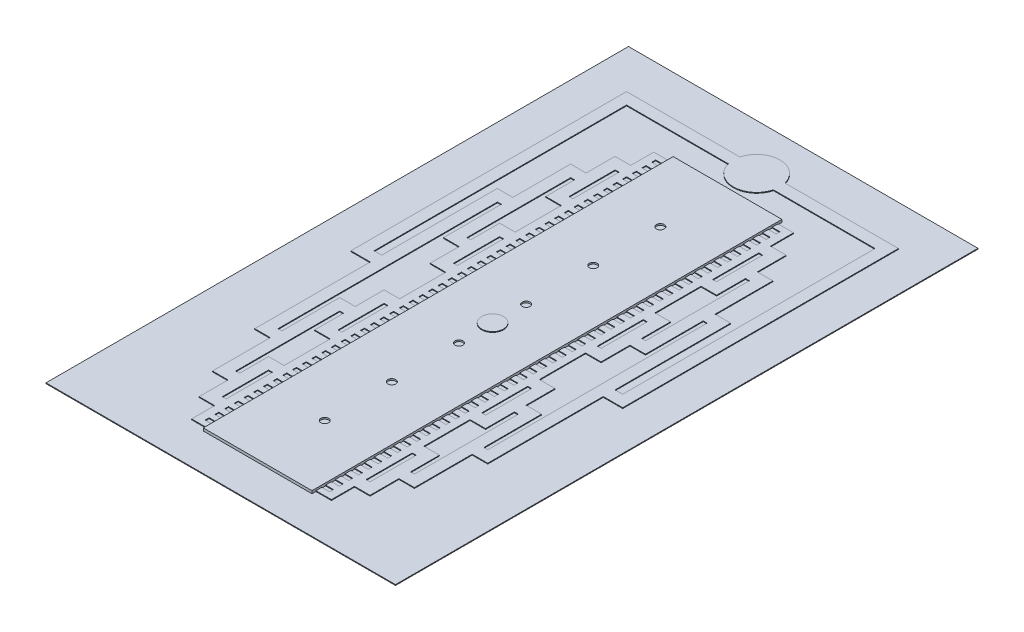
SolidWorks part; units mm, degrees
ref_plane "Front Plane" through (0, 0, 0) normal (0, 0, 1) x (1, 0, 0)
ref_plane "Top Plane" through (0, 0, 0) normal (0, 1, 0) x (1, 0, 0)
ref_plane "Right Plane" through (0, 0, 0) normal (1, 0, 0) x (0, 0, -1)
sketch "Sketch2" plane through (0, 0, 0) normal (0, 1, 0) x (1, 0, 0)
  line L1 (-22.5, 37.5) -> (22.5, 37.5)
  line L2 (-22.5, 37.5) -> (-22.5, -37.5)
  line L3 (-22.5, -37.5) -> (22.5, -37.5)
  line L4 (22.5, 37.5) -> (22.5, -37.5)
  line L5 (-22.5, 37.5) -> (22.5, -37.5) construction
  line L6 (-22.5, -37.5) -> (22.5, 37.5) construction
  point P0 (0, 0)
extrude "Boss-Extrude1" add sketch "Sketch2" along normal blind 0.1
sketch "Sketch3" plane through (0, 0.1, 0) normal (0, 1, 0) x (1, 0, 0)
  line L1 (-7, 30.25) -> (7, 30.25)
  line L2 (-7, 30.25) -> (-7, -30.25)
  line L3 (-7, -30.25) -> (7, -30.25)
  line L4 (7, 30.25) -> (7, -30.25)
  line L5 (-7, 30.25) -> (7, -30.25) construction
  line L6 (-7, -30.25) -> (7, 30.25) construction
  point P0 (0, 0)
extrude "Boss-Extrude2" add sketch "Sketch3" along normal blind 0.35
sketch "Sketch4" plane through (0, 0.1, 0) normal (0, 1, 0) x (1, 0, 0)
  line L0 (7, 29.75) -> (9, 29.75)
  line L1 (7, 29.75) -> (7, -29.75)
  line L2 (9, 29.75) -> (9, -29.75)
  line L3 (7, -29.75) -> (9, -29.75)
  line L4 (7, -30.25) -> (7, 30.25) construction
  line L5 (0, 31.7119) -> (0, -31.7119) construction
  line L6 (-9, 29.75) -> (-9, -29.75)
  line L7 (-7, -29.75) -> (-9, -29.75)
  line L8 (-7, 29.75) -> (-7, -29.75)
  line L9 (-7, 29.75) -> (-9, 29.75)
  point P6 (9, 0)
  point P11 (0, 0)
extrude "Boss-Extrude3" add sketch "Sketch4" along normal blind 0.1
sketch "Sketch5" plane through (0, 0.2, 0) normal (0, 1, 0) x (1, 0, 0)
  line L0 (7, 29) -> (8, 29)
  line L1 (7, 29) -> (7, 28.5)
  line L2 (8, 29) -> (8, 28.5)
  line L3 (7, 28.5) -> (8, 28.5)
  line L4 (7, -30.25) -> (7, 30.25) construction
  line L5 (-8, 29) -> (-7, 29)
  line L6 (-8, 29) -> (-8, 28.5)
  line L7 (-8, 28.5) -> (-7, 28.5)
  line L8 (-7, 29) -> (-7, 28.5)
  line L9 (-8, 27.75) -> (-7, 27.75)
  line L10 (-8, 27.75) -> (-8, 27.25)
  line L11 (-8, 27.25) -> (-7, 27.25)
  line L12 (-7, 27.75) -> (-7, 27.25)
  line L13 (-8, 26.5) -> (-7, 26.5)
  line L14 (-8, 26.5) -> (-8, 26)
  line L15 (-8, 26) -> (-7, 26)
  line L16 (-7, 26.5) -> (-7, 26)
  line L17 (-8, 25.25) -> (-7, 25.25)
  line L18 (-8, 25.25) -> (-8, 24.75)
  line L19 (-8, 24.75) -> (-7, 24.75)
  line L20 (-7, 25.25) -> (-7, 24.75)
  line L21 (-8, 24) -> (-7, 24)
  line L22 (-8, 24) -> (-8, 23.5)
  line L23 (-8, 23.5) -> (-7, 23.5)
  line L24 (-7, 24) -> (-7, 23.5)
  line L25 (-8, 22.75) -> (-7, 22.75)
  line L26 (-8, 22.75) -> (-8, 22.25)
  line L27 (-8, 22.25) -> (-7, 22.25)
  line L28 (-7, 22.75) -> (-7, 22.25)
  line L29 (-8, 21.5) -> (-7, 21.5)
  line L30 (-8, 21.5) -> (-8, 21)
  line L31 (-8, 21) -> (-7, 21)
  line L32 (-7, 21.5) -> (-7, 21)
  line L33 (-8, 20.25) -> (-7, 20.25)
  line L34 (-8, 20.25) -> (-8, 19.75)
  line L35 (-8, 19.75) -> (-7, 19.75)
  line L36 (-7, 20.25) -> (-7, 19.75)
  line L37 (-8, 19) -> (-7, 19)
  line L38 (-8, 19) -> (-8, 18.5)
  line L39 (-8, 18.5) -> (-7, 18.5)
  line L40 (-7, 19) -> (-7, 18.5)
  line L41 (-8, 17.75) -> (-7, 17.75)
  line L42 (-8, 17.75) -> (-8, 17.25)
  line L43 (-8, 17.25) -> (-7, 17.25)
  line L44 (-7, 17.75) -> (-7, 17.25)
  line L45 (-8, 16.5) -> (-7, 16.5)
  line L46 (-8, 16.5) -> (-8, 16)
  line L47 (-8, 16) -> (-7, 16)
  line L48 (-7, 16.5) -> (-7, 16)
  line L49 (-8, 15.25) -> (-7, 15.25)
  line L50 (-8, 15.25) -> (-8, 14.75)
  line L51 (-8, 14.75) -> (-7, 14.75)
  line L52 (-7, 15.25) -> (-7, 14.75)
  line L53 (-8, 14) -> (-7, 14)
  line L54 (-8, 14) -> (-8, 13.5)
  line L55 (-8, 13.5) -> (-7, 13.5)
  line L56 (-7, 14) -> (-7, 13.5)
  line L57 (-8, 12.75) -> (-7, 12.75)
  line L58 (-8, 12.75) -> (-8, 12.25)
  line L59 (-8, 12.25) -> (-7, 12.25)
  line L60 (-7, 12.75) -> (-7, 12.25)
  line L61 (-8, 11.5) -> (-7, 11.5)
  line L62 (-8, 11.5) -> (-8, 11)
  line L63 (-8, 11) -> (-7, 11)
  line L64 (-7, 11.5) -> (-7, 11)
  line L65 (-8, 10.25) -> (-7, 10.25)
  line L66 (-8, 10.25) -> (-8, 9.75)
  line L67 (-8, 9.75) -> (-7, 9.75)
  line L68 (-7, 10.25) -> (-7, 9.75)
  line L69 (-8, 9) -> (-7, 9)
  line L70 (-8, 9) -> (-8, 8.5)
  line L71 (-8, 8.5) -> (-7, 8.5)
  line L72 (-7, 9) -> (-7, 8.5)
  line L73 (-8, 7.75) -> (-7, 7.75)
  line L74 (-8, 7.75) -> (-8, 7.25)
  line L75 (-8, 7.25) -> (-7, 7.25)
  line L76 (-7, 7.75) -> (-7, 7.25)
  line L77 (-8, 6.5) -> (-7, 6.5)
  line L78 (-8, 6.5) -> (-8, 6)
  line L79 (-8, 6) -> (-7, 6)
  line L80 (-7, 6.5) -> (-7, 6)
  line L81 (-8, 5.25) -> (-7, 5.25)
  line L82 (-8, 5.25) -> (-8, 4.75)
  line L83 (-8, 4.75) -> (-7, 4.75)
  line L84 (-7, 5.25) -> (-7, 4.75)
  line L85 (-8, 4) -> (-7, 4)
  line L86 (-8, 4) -> (-8, 3.5)
  line L87 (-8, 3.5) -> (-7, 3.5)
  line L88 (-7, 4) -> (-7, 3.5)
  line L89 (-8, 2.75) -> (-7, 2.75)
  line L90 (-8, 2.75) -> (-8, 2.25)
  line L91 (-8, 2.25) -> (-7, 2.25)
  line L92 (-7, 2.75) -> (-7, 2.25)
  line L93 (-8, 1.5) -> (-7, 1.5)
  line L94 (-8, 1.5) -> (-8, 1)
  line L95 (-8, 1) -> (-7, 1)
  line L96 (-7, 1.5) -> (-7, 1)
  line L97 (-8, 0.25) -> (-7, 0.25)
  line L98 (-8, 0.25) -> (-8, -0.25)
  line L99 (-8, -0.25) -> (-7, -0.25)
  line L100 (-7, 0.25) -> (-7, -0.25)
  line L101 (-8, -1) -> (-7, -1)
  line L102 (-8, -1) -> (-8, -1.5)
  line L103 (-8, -1.5) -> (-7, -1.5)
  line L104 (-7, -1) -> (-7, -1.5)
  line L105 (-8, -2.25) -> (-7, -2.25)
  line L106 (-8, -2.25) -> (-8, -2.75)
  line L107 (-8, -2.75) -> (-7, -2.75)
  line L108 (-7, -2.25) -> (-7, -2.75)
  line L109 (-8, -3.5) -> (-7, -3.5)
  line L110 (-8, -3.5) -> (-8, -4)
  line L111 (-8, -4) -> (-7, -4)
  line L112 (-7, -3.5) -> (-7, -4)
  line L113 (-8, -4.75) -> (-7, -4.75)
  line L114 (-8, -4.75) -> (-8, -5.25)
  line L115 (-8, -5.25) -> (-7, -5.25)
  line L116 (-7, -4.75) -> (-7, -5.25)
  line L117 (-8, -6) -> (-7, -6)
  line L118 (-8, -6) -> (-8, -6.5)
  line L119 (-8, -6.5) -> (-7, -6.5)
  line L120 (-7, -6) -> (-7, -6.5)
  line L121 (-8, -7.25) -> (-7, -7.25)
  line L122 (-8, -7.25) -> (-8, -7.75)
  line L123 (-8, -7.75) -> (-7, -7.75)
  line L124 (-7, -7.25) -> (-7, -7.75)
  line L125 (-8, -8.5) -> (-7, -8.5)
  line L126 (-8, -8.5) -> (-8, -9)
  line L127 (-8, -9) -> (-7, -9)
  line L128 (-7, -8.5) -> (-7, -9)
  line L129 (-8, -9.75) -> (-7, -9.75)
  line L130 (-8, -9.75) -> (-8, -10.25)
  line L131 (-8, -10.25) -> (-7, -10.25)
  line L132 (-7, -9.75) -> (-7, -10.25)
  line L133 (-8, -11) -> (-7, -11)
  line L134 (-8, -11) -> (-8, -11.5)
  line L135 (-8, -11.5) -> (-7, -11.5)
  line L136 (-7, -11) -> (-7, -11.5)
  line L137 (-8, -12.25) -> (-7, -12.25)
  line L138 (-8, -12.25) -> (-8, -12.75)
  line L139 (-8, -12.75) -> (-7, -12.75)
  line L140 (-7, -12.25) -> (-7, -12.75)
  line L141 (-8, -13.5) -> (-7, -13.5)
  line L142 (-8, -13.5) -> (-8, -14)
  line L143 (-8, -14) -> (-7, -14)
  line L144 (-7, -13.5) -> (-7, -14)
  line L145 (-8, -14.75) -> (-7, -14.75)
  line L146 (-8, -14.75) -> (-8, -15.25)
  line L147 (-8, -15.25) -> (-7, -15.25)
  line L148 (-7, -14.75) -> (-7, -15.25)
  line L149 (-8, -16) -> (-7, -16)
  line L150 (-8, -16) -> (-8, -16.5)
  line L151 (-8, -16.5) -> (-7, -16.5)
  line L152 (-7, -16) -> (-7, -16.5)
  line L153 (-8, -17.25) -> (-7, -17.25)
  line L154 (-8, -17.25) -> (-8, -17.75)
  line L155 (-8, -17.75) -> (-7, -17.75)
  line L156 (-7, -17.25) -> (-7, -17.75)
  line L157 (-8, -18.5) -> (-7, -18.5)
  line L158 (-8, -18.5) -> (-8, -19)
  line L159 (-8, -19) -> (-7, -19)
  line L160 (-7, -18.5) -> (-7, -19)
  line L161 (-8, -19.75) -> (-7, -19.75)
  line L162 (-8, -19.75) -> (-8, -20.25)
  line L163 (-8, -20.25) -> (-7, -20.25)
  line L164 (-7, -19.75) -> (-7, -20.25)
  line L165 (-8, -21) -> (-7, -21)
  line L166 (-8, -21) -> (-8, -21.5)
  line L167 (-8, -21.5) -> (-7, -21.5)
  line L168 (-7, -21) -> (-7, -21.5)
  line L169 (-8, -22.25) -> (-7, -22.25)
  line L170 (-8, -22.25) -> (-8, -22.75)
  line L171 (-8, -22.75) -> (-7, -22.75)
  line L172 (-7, -22.25) -> (-7, -22.75)
  line L173 (-8, -23.5) -> (-7, -23.5)
  line L174 (-8, -23.5) -> (-8, -24)
  line L175 (-8, -24) -> (-7, -24)
  line L176 (-7, -23.5) -> (-7, -24)
  line L177 (-8, -24.75) -> (-7, -24.75)
  line L178 (-8, -24.75) -> (-8, -25.25)
  line L179 (-8, -25.25) -> (-7, -25.25)
  line L180 (-7, -24.75) -> (-7, -25.25)
  line L181 (-8, -26) -> (-7, -26)
  line L182 (-8, -26) -> (-8, -26.5)
  line L183 (-8, -26.5) -> (-7, -26.5)
  line L184 (-7, -26) -> (-7, -26.5)
  line L185 (-8, -27.25) -> (-7, -27.25)
  line L186 (-8, -27.25) -> (-8, -27.75)
  line L187 (-8, -27.75) -> (-7, -27.75)
  line L188 (-7, -27.25) -> (-7, -27.75)
  line L189 (-8, -28.5) -> (-7, -28.5)
  line L190 (-8, -28.5) -> (-8, -29)
  line L191 (-8, -29) -> (-7, -29)
  line L192 (-7, -28.5) -> (-7, -29)
  line L193 (7, 27.75) -> (8, 27.75)
  line L194 (7, 27.75) -> (7, 27.25)
  line L195 (7, 27.25) -> (8, 27.25)
  line L196 (8, 27.75) -> (8, 27.25)
  line L197 (7, 26.5) -> (8, 26.5)
  line L198 (7, 26.5) -> (7, 26)
  line L199 (7, 26) -> (8, 26)
  line L200 (8, 26.5) -> (8, 26)
  line L201 (7, 25.25) -> (8, 25.25)
  line L202 (7, 25.25) -> (7, 24.75)
  line L203 (7, 24.75) -> (8, 24.75)
  line L204 (8, 25.25) -> (8, 24.75)
  line L205 (7, 24) -> (8, 24)
  line L206 (7, 24) -> (7, 23.5)
  line L207 (7, 23.5) -> (8, 23.5)
  line L208 (8, 24) -> (8, 23.5)
  line L209 (7, 22.75) -> (8, 22.75)
  line L210 (7, 22.75) -> (7, 22.25)
  line L211 (7, 22.25) -> (8, 22.25)
  line L212 (8, 22.75) -> (8, 22.25)
  line L213 (7, 21.5) -> (8, 21.5)
  line L214 (7, 21.5) -> (7, 21)
  line L215 (7, 21) -> (8, 21)
  line L216 (8, 21.5) -> (8, 21)
  line L217 (7, 20.25) -> (8, 20.25)
  line L218 (7, 20.25) -> (7, 19.75)
  line L219 (7, 19.75) -> (8, 19.75)
  line L220 (8, 20.25) -> (8, 19.75)
  line L221 (7, 19) -> (8, 19)
  line L222 (7, 19) -> (7, 18.5)
  line L223 (7, 18.5) -> (8, 18.5)
  line L224 (8, 19) -> (8, 18.5)
  line L225 (7, 17.75) -> (8, 17.75)
  line L226 (7, 17.75) -> (7, 17.25)
  line L227 (7, 17.25) -> (8, 17.25)
  line L228 (8, 17.75) -> (8, 17.25)
  line L229 (7, 16.5) -> (8, 16.5)
  line L230 (7, 16.5) -> (7, 16)
  line L231 (7, 16) -> (8, 16)
  line L232 (8, 16.5) -> (8, 16)
  line L233 (7, 15.25) -> (8, 15.25)
  line L234 (7, 15.25) -> (7, 14.75)
  line L235 (7, 14.75) -> (8, 14.75)
  line L236 (8, 15.25) -> (8, 14.75)
  line L237 (7, 14) -> (8, 14)
  line L238 (7, 14) -> (7, 13.5)
  line L239 (7, 13.5) -> (8, 13.5)
  line L240 (8, 14) -> (8, 13.5)
  line L241 (7, 12.75) -> (8, 12.75)
  line L242 (7, 12.75) -> (7, 12.25)
  line L243 (7, 12.25) -> (8, 12.25)
  line L244 (8, 12.75) -> (8, 12.25)
  line L245 (7, 11.5) -> (8, 11.5)
  line L246 (7, 11.5) -> (7, 11)
  line L247 (7, 11) -> (8, 11)
  line L248 (8, 11.5) -> (8, 11)
  line L249 (7, 10.25) -> (8, 10.25)
  line L250 (7, 10.25) -> (7, 9.75)
  line L251 (7, 9.75) -> (8, 9.75)
  line L252 (8, 10.25) -> (8, 9.75)
  line L253 (7, 9) -> (8, 9)
  line L254 (7, 9) -> (7, 8.5)
  line L255 (7, 8.5) -> (8, 8.5)
  line L256 (8, 9) -> (8, 8.5)
  line L257 (7, 7.75) -> (8, 7.75)
  line L258 (7, 7.75) -> (7, 7.25)
  line L259 (7, 7.25) -> (8, 7.25)
  line L260 (8, 7.75) -> (8, 7.25)
  line L261 (7, 6.5) -> (8, 6.5)
  line L262 (7, 6.5) -> (7, 6)
  line L263 (7, 6) -> (8, 6)
  line L264 (8, 6.5) -> (8, 6)
  line L265 (7, 5.25) -> (8, 5.25)
  line L266 (7, 5.25) -> (7, 4.75)
  line L267 (7, 4.75) -> (8, 4.75)
  line L268 (8, 5.25) -> (8, 4.75)
  line L269 (7, 4) -> (8, 4)
  line L270 (7, 4) -> (7, 3.5)
  line L271 (7, 3.5) -> (8, 3.5)
  line L272 (8, 4) -> (8, 3.5)
  line L273 (7, 2.75) -> (8, 2.75)
  line L274 (7, 2.75) -> (7, 2.25)
  line L275 (7, 2.25) -> (8, 2.25)
  line L276 (8, 2.75) -> (8, 2.25)
  line L277 (7, 1.5) -> (8, 1.5)
  line L278 (7, 1.5) -> (7, 1)
  line L279 (7, 1) -> (8, 1)
  line L280 (8, 1.5) -> (8, 1)
  line L281 (7, 0.25) -> (8, 0.25)
  line L282 (7, 0.25) -> (7, -0.25)
  line L283 (7, -0.25) -> (8, -0.25)
  line L284 (8, 0.25) -> (8, -0.25)
  line L285 (7, -1) -> (8, -1)
  line L286 (7, -1) -> (7, -1.5)
  line L287 (7, -1.5) -> (8, -1.5)
  line L288 (8, -1) -> (8, -1.5)
  line L289 (7, -2.25) -> (8, -2.25)
  line L290 (7, -2.25) -> (7, -2.75)
  line L291 (7, -2.75) -> (8, -2.75)
  line L292 (8, -2.25) -> (8, -2.75)
  line L293 (7, -3.5) -> (8, -3.5)
  line L294 (7, -3.5) -> (7, -4)
  line L295 (7, -4) -> (8, -4)
  line L296 (8, -3.5) -> (8, -4)
  line L297 (7, -4.75) -> (8, -4.75)
  line L298 (7, -4.75) -> (7, -5.25)
  line L299 (7, -5.25) -> (8, -5.25)
  line L300 (8, -4.75) -> (8, -5.25)
  line L301 (7, -6) -> (8, -6)
  line L302 (7, -6) -> (7, -6.5)
  line L303 (7, -6.5) -> (8, -6.5)
  line L304 (8, -6) -> (8, -6.5)
  line L305 (7, -7.25) -> (8, -7.25)
  line L306 (7, -7.25) -> (7, -7.75)
  line L307 (7, -7.75) -> (8, -7.75)
  line L308 (8, -7.25) -> (8, -7.75)
  line L309 (7, -8.5) -> (8, -8.5)
  line L310 (7, -8.5) -> (7, -9)
  line L311 (7, -9) -> (8, -9)
  line L312 (8, -8.5) -> (8, -9)
  line L313 (7, -9.75) -> (8, -9.75)
  line L314 (7, -9.75) -> (7, -10.25)
  line L315 (7, -10.25) -> (8, -10.25)
  line L316 (8, -9.75) -> (8, -10.25)
  line L317 (7, -11) -> (8, -11)
  line L318 (7, -11) -> (7, -11.5)
  line L319 (7, -11.5) -> (8, -11.5)
  line L320 (8, -11) -> (8, -11.5)
  line L321 (7, -12.25) -> (8, -12.25)
  line L322 (7, -12.25) -> (7, -12.75)
  line L323 (7, -12.75) -> (8, -12.75)
  line L324 (8, -12.25) -> (8, -12.75)
  line L325 (7, -13.5) -> (8, -13.5)
  line L326 (7, -13.5) -> (7, -14)
  line L327 (7, -14) -> (8, -14)
  line L328 (8, -13.5) -> (8, -14)
  line L329 (7, -14.75) -> (8, -14.75)
  line L330 (7, -14.75) -> (7, -15.25)
  line L331 (7, -15.25) -> (8, -15.25)
  line L332 (8, -14.75) -> (8, -15.25)
  line L333 (7, -16) -> (8, -16)
  line L334 (7, -16) -> (7, -16.5)
  line L335 (7, -16.5) -> (8, -16.5)
  line L336 (8, -16) -> (8, -16.5)
  line L337 (7, -17.25) -> (8, -17.25)
  line L338 (7, -17.25) -> (7, -17.75)
  line L339 (7, -17.75) -> (8, -17.75)
  line L340 (8, -17.25) -> (8, -17.75)
  line L341 (7, -18.5) -> (8, -18.5)
  line L342 (7, -18.5) -> (7, -19)
  line L343 (7, -19) -> (8, -19)
  line L344 (8, -18.5) -> (8, -19)
  line L345 (7, -19.75) -> (8, -19.75)
  line L346 (7, -19.75) -> (7, -20.25)
  line L347 (7, -20.25) -> (8, -20.25)
  line L348 (8, -19.75) -> (8, -20.25)
  line L349 (7, -21) -> (8, -21)
  line L350 (7, -21) -> (7, -21.5)
  line L351 (7, -21.5) -> (8, -21.5)
  line L352 (8, -21) -> (8, -21.5)
  line L353 (7, -22.25) -> (8, -22.25)
  line L354 (7, -22.25) -> (7, -22.75)
  line L355 (7, -22.75) -> (8, -22.75)
  line L356 (8, -22.25) -> (8, -22.75)
  line L357 (7, -23.5) -> (8, -23.5)
  line L358 (7, -23.5) -> (7, -24)
  line L359 (7, -24) -> (8, -24)
  line L360 (8, -23.5) -> (8, -24)
  line L361 (7, -24.75) -> (8, -24.75)
  line L362 (7, -24.75) -> (7, -25.25)
  line L363 (7, -25.25) -> (8, -25.25)
  line L364 (8, -24.75) -> (8, -25.25)
  line L365 (7, -26) -> (8, -26)
  line L366 (7, -26) -> (7, -26.5)
  line L367 (7, -26.5) -> (8, -26.5)
  line L368 (8, -26) -> (8, -26.5)
  line L369 (7, -27.25) -> (8, -27.25)
  line L370 (7, -27.25) -> (7, -27.75)
  line L371 (7, -27.75) -> (8, -27.75)
  line L372 (8, -27.25) -> (8, -27.75)
  line L373 (7, -28.5) -> (8, -28.5)
  line L374 (7, -28.5) -> (7, -29)
  line L375 (7, -29) -> (8, -29)
  line L376 (8, -28.5) -> (8, -29)
  dimension "D1" = 0.75
  dimension "D2" = 2
  dimension "D3" = 47
extrude "Cut-Extrude1" cut sketch "Sketch5" against normal blind 0.1
sketch "Sketch6" plane through (0, 0.1, 0) normal (0, 1, 0) x (1, 0, 0)
  line L0 (0, -32.9565) -> (0, 32.9565) construction
  line L1 (-17.9872, 0) -> (17.9872, 0) construction
  line L2 (7, 30.25) -> (-7, 30.25) construction
  line L3 (-17.5, 34.75) -> (17.5, 34.75)
  line L4 (-16, 33.25) -> (16, 33.25)
  line L5 (-17.5, 34.75) -> (-17.5, -0.75)
  line L6 (-16, 33.25) -> (-16, 0.75)
  line L7 (-17.5, -0.75) -> (-15, -0.75)
  line L8 (-16, 0.75) -> (-15.0229, 0.75)
  line L9 (-9, 29.75) -> (-9, -29.75) construction
  line L10 (-9, 26.7813) -> (-11.0229, 26.7813)
  line L11 (-9, 25.2813) -> (-9.5, 25.2813)
  line L12 (-9, 17.8438) -> (-11, 17.8438)
  line L13 (-9, 19.3438) -> (-9.5, 19.3438)
  line L14 (-9.5, 19.3438) -> (-9.5, 25.2813)
  line L15 (-11.0229, 23.0625) -> (-11.0229, 26.7813)
  line L16 (-11, 21.5625) -> (-11, 17.8438)
  line L17 (-9, 29.75) -> (-9, -29.75) construction
  line L18 (-9, 2.9688) -> (-11, 2.9688)
  line L19 (-9, 4.4688) -> (-9.5, 4.4688)
  line L20 (-9, 11.9063) -> (-11, 11.9063)
  line L21 (-9, 10.4063) -> (-9.5, 10.4063)
  line L22 (-9.5, 10.4063) -> (-9.5, 4.4688)
  line L23 (-11, 2.9688) -> (-11, 6.6875)
  line L24 (-11, 8.1875) -> (-11, 11.9063)
  line L25 (-9, -2.9687) -> (-11, -2.9687)
  line L26 (-9, -4.4687) -> (-9.5, -4.4687)
  line L27 (-9, -11.9062) -> (-11, -11.9062)
  line L28 (-9, -10.4062) -> (-9.5, -10.4062)
  line L29 (-9.5, -10.4062) -> (-9.5, -4.4687)
  line L30 (-11, -11.9062) -> (-11, -8.1875)
  line L31 (-9, -17.8437) -> (-11, -17.8437)
  line L32 (-11, -6.6875) -> (-11, -2.9687)
  line L33 (-9, -19.3437) -> (-9.5, -19.3437)
  line L34 (-9, -26.7812) -> (-11, -26.7812)
  line L35 (-9, -25.2812) -> (-9.5, -25.2812)
  line L36 (-9.5, -25.2812) -> (-9.5, -19.3437)
  line L37 (-11, -17.8437) -> (-11, -21.5625)
  line L38 (-11, -23.0625) -> (-11, -26.7812)
  line L39 (-9, -22.3125) -> (-11.344, -22.3125) construction
  line L40 (-9, -7.4375) -> (-11.3125, -7.4375) construction
  line L41 (-9, 7.4375) -> (-11.3125, 7.4375) construction
  line L42 (-9, 22.3125) -> (-11.3125, 22.3125) construction
  line L43 (-11.0229, 23.0625) -> (-13.0229, 23.0625)
  line L44 (-11, 21.5625) -> (-11.5, 21.5625)
  line L45 (-11, 6.6875) -> (-13, 6.6875)
  line L46 (-11, 8.1875) -> (-11.5, 8.1875)
  line L47 (-11.5, 8.1875) -> (-11.5, 21.5625)
  line L48 (-13.0229, 23.0625) -> (-13.0229, 15.625)
  line L49 (-13, 14.125) -> (-13, 6.6875)
  line L50 (-11, -6.6875) -> (-13, -6.6875)
  line L51 (-11, -8.1875) -> (-11.5, -8.1875)
  line L52 (-11, -23.0625) -> (-13, -23.0625)
  line L53 (-11, -21.5625) -> (-11.5, -21.5625)
  line L54 (-11.5, -21.5625) -> (-11.5, -8.1875)
  line L55 (-13, -6.6875) -> (-13, -14.125)
  line L56 (-13, -15.625) -> (-13, -23.0625)
  line L57 (-9, 14.875) -> (-13.3781, 14.875) construction
  line L58 (-9, -14.875) -> (-13.151, -14.875) construction
  line L59 (-13, -15.625) -> (-15, -15.625)
  line L60 (-13, -14.125) -> (-13.5, -14.125)
  line L61 (-13.0229, 15.625) -> (-15.0229, 15.625)
  line L62 (-13, 14.125) -> (-13.5, 14.125)
  line L63 (-13.5, 14.125) -> (-13.5, -14.125)
  line L64 (-15, -15.625) -> (-15, -0.75)
  line L65 (-15.0229, 0.75) -> (-15.0229, 15.625)
  line L66 (9, 25.2813) -> (9.5, 25.2813)
  line L67 (11.0229, 23.0625) -> (11.0229, 26.7813)
  line L68 (9, 26.7813) -> (11.0229, 26.7813)
  line L69 (11.0229, 23.0625) -> (13.0229, 23.0625)
  line L70 (11, 21.5625) -> (11.5, 21.5625)
  line L71 (9.5, 19.3438) -> (9.5, 25.2813)
  line L72 (9, 19.3438) -> (9.5, 19.3438)
  line L73 (11, 21.5625) -> (11, 17.8438)
  line L74 (9, 17.8438) -> (11, 17.8438)
  line L75 (13.0229, 23.0625) -> (13.0229, 15.625)
  line L76 (13, 14.125) -> (13.5, 14.125)
  line L77 (13.0229, 15.625) -> (15.0229, 15.625)
  line L78 (9, 10.4063) -> (9.5, 10.4063)
  line L79 (9, 11.9063) -> (11, 11.9063)
  line L80 (11, 8.1875) -> (11, 11.9063)
  line L81 (11.5, 8.1875) -> (11.5, 21.5625)
  line L82 (11, 8.1875) -> (11.5, 8.1875)
  line L83 (13, 14.125) -> (13, 6.6875)
  line L84 (11, 6.6875) -> (13, 6.6875)
  line L85 (9, 4.4688) -> (9.5, 4.4688)
  line L86 (9.5, 10.4063) -> (9.5, 4.4688)
  line L87 (11, 2.9688) -> (11, 6.6875)
  line L88 (9, 2.9688) -> (11, 2.9688)
  line L89 (17.5, 34.75) -> (17.5, -0.75)
  line L90 (15.0229, 0.75) -> (15.0229, 15.625)
  line L91 (16, 33.25) -> (16, 0.75)
  line L92 (16, 0.75) -> (15.0229, 0.75)
  line L93 (17.5, -0.75) -> (15, -0.75)
  line L94 (9, -2.9687) -> (11, -2.9687)
  line L95 (9, -10.4062) -> (9.5, -10.4062)
  line L96 (9, -4.4687) -> (9.5, -4.4687)
  line L97 (11, -6.6875) -> (11, -2.9687)
  line L98 (11, -6.6875) -> (13, -6.6875)
  line L99 (11, -8.1875) -> (11.5, -8.1875)
  line L100 (9.5, -10.4062) -> (9.5, -4.4687)
  line L101 (11, -11.9062) -> (11, -8.1875)
  line L102 (9, -11.9062) -> (11, -11.9062)
  line L103 (13, -6.6875) -> (13, -14.125)
  line L104 (15, -15.625) -> (15, -0.75)
  line L105 (13.5, 14.125) -> (13.5, -14.125)
  line L106 (13, -15.625) -> (15, -15.625)
  line L107 (13, -14.125) -> (13.5, -14.125)
  line L108 (9, -17.8437) -> (11, -17.8437)
  line L109 (9, -19.3437) -> (9.5, -19.3437)
  line L110 (11, -17.8437) -> (11, -21.5625)
  line L111 (11.5, -21.5625) -> (11.5, -8.1875)
  line L112 (13, -15.625) -> (13, -23.0625)
  line L113 (11, -23.0625) -> (13, -23.0625)
  line L114 (11, -21.5625) -> (11.5, -21.5625)
  line L115 (9.5, -25.2812) -> (9.5, -19.3437)
  line L116 (11, -23.0625) -> (11, -26.7812)
  line L117 (9, -26.7812) -> (11, -26.7812)
  line L118 (9, -25.2812) -> (9.5, -25.2812)
  circle A0 centre (0, 34) radius 3
  point P0 (0, 30.25)
  point P4 (0, 0)
  point P8 (0, 0)
  point P9 (0, 34)
  point P14 (0, 33.25)
  point P15 (0, 34.75)
  point P16 (-16, 0)
  point P19 (0, 34.75)
  point P22 (0, 33.25)
  point P24 (-17.5, 0)
  point P26 (-9, 29.75)
  point P29 (-9, 26.7813)
  point P31 (-9, 25.2813)
  point P32 (-9, 26.0313)
  point P33 (-9, 22.3125)
  point P34 (-9, 18.5938)
  point P35 (-9, 14.875)
  point P36 (-9, 11.1563)
  point P37 (-9, 7.4375)
  point P38 (-9, 3.7188)
  point P39 (-9, 0)
  point P40 (-9, -3.7187)
  point P41 (-9, -7.4375)
  point P42 (-9, -11.1562)
  point P43 (-9, -14.875)
  point P44 (-9, -18.5937)
  point P45 (-9, -22.3125)
  point P46 (-9, -26.0312)
  point P47 (-9, -29.75)
  point P54 (-9, 19.3438)
  point P55 (-9, 17.8438)
  point P65 (-9, 11.9063)
  point P66 (-9, 10.4063)
  point P69 (-9, 4.4688)
  point P70 (-9, 2.9688)
  point P81 (-9, -2.9687)
  point P82 (-9, -4.4687)
  point P87 (-9, -10.4062)
  point P88 (-9, -11.9062)
  point P93 (-9, -17.8437)
  point P96 (-9, -19.3437)
  point P101 (-9, -25.2812)
  point P102 (-9, -26.7812)
  point P125 (-11, -7.4375)
  point P126 (-11, -22.3125)
  point P137 (-13, -14.875)
  line M5 (-9, -29.75) -> (-9, 29.75)
  line M11 (9, 29.75) -> (9, -29.75)
  dimension "D2" = 0.75
  dimension "D4" = 0.75
  dimension "D5" = 0.75
  dimension "D1" = 3.75
  dimension "D3" = 0.75
  dimension "D6" = 17
  dimension "D7" = 0.75
  dimension "D8" = 0.75
  dimension "D9" = 0.75
  dimension "D10" = 0.75
  dimension "D11" = 0.75
  dimension "D12" = 0.75
  dimension "D13" = 0.75
  dimension ".75" = 0.75
  dimension "D14" = 0.75
  dimension "D15" = 0.75
  dimension "D16" = 0.75
  dimension "D17" = 0.75
  dimension "D18" = 0.75
  dimension "D19" = 0.75
  dimension "D20" = 0.75
  dimension "D21" = 0.75
extrude "Boss-Extrude4" add sketch "Sketch6" along normal blind 0.1 contours A0 L4 L91 L92 L90 L77 L75 L69 L67 L68 L66 L71 L72 L74 L73 L70 L81 L82 L80 L79 L78 L86 L85 L88 L87 L84 L83 L76 L105 L107 L103 L98 L97 L94 L96 L100 L95 L102 L101 L99 L111 L114 L110 L108 M11 | A0 L3 L5 L7 L64 L59 L56 L52 L38 L34 L35 L36 L33 L31 L37 L53 L54 L51 L30 L27 L28 L29 L26 L25 L32 L50 L55 L60 L63 L62 L49 L45 L23 L18 L19 L22 L21 L20 L24 L46 L47 L44 L16 L12 M5 | L4 A0 L3 | L3 A0 | L4 A0 region at (-12.924, 0.1, -6.7147) region at (0, 0.1, -35.6871) region at (0, 0.1, -34) region at (12.924, 0.1, -6.7147) region at (0, 0.1, -32.3129)
sketch "Sketch7" plane through (0, 0.45, 0) normal (0, 1, 0) x (1, 0, 0)
  circle A0 centre (0, 0) radius 1.4
extrude "Boss-Extrude5" add sketch "Sketch7" along normal blind 0.1
sketch "Sketch8" plane through (0, 0.45, 0) normal (0, 1, 0) x (1, 0, 0)
  line L0 (0, 29.6213) -> (0, -29.6213) construction
  line L1 (7, 30.25) -> (-7, 30.25) construction
  circle A0 centre (0, 21.6071) radius 0.5
  circle A1 centre (0, 12.9643) radius 0.5
  circle A2 centre (0, 4.3214) radius 0.5
  circle A3 centre (0, -4.3214) radius 0.5
  circle A4 centre (0, -12.9643) radius 0.5
  circle A5 centre (0, -21.6071) radius 0.5
  point P0 (0, 21.6071)
  point P5 (0, 0)
  point P7 (0, 30.25)
  dimension "D2" = 6
  dimension "D1" = 8.6429
extrude "Cut-Extrude2" cut sketch "Sketch8" against normal blind 0.2
sketch "Sketch9" plane through (0, 0, 37.5) normal (0, 0, 1) x (1, 0, 0)
  line L0 (22.5, 0.1) -> (22.5, 0)
  line L1 (22.5, 0.1) -> (-22.5037, 0.1)
  line L2 (22.5, 0) -> (-22.5037, 0)
  line L3 (-22.5037, 0.1) -> (-22.5037, 0)
extrude "Cut-Extrude3" cut sketch "Sketch9" against normal blind 2.5
sketch "Sketch10" plane through (0, 0, -37.5) normal (0, 0, -1) x (-1, 0, 0)
  line L0 (-22.5, 0.1) -> (-22.5, 0)
  line L1 (-22.5, 0.1) -> (22.5017, 0.1)
  line L2 (-22.5, 0) -> (22.5017, 0)
  line L3 (22.5017, 0.1) -> (22.5017, 0)
extrude "Boss-Extrude6" add sketch "Sketch10" along normal blind 2.5
